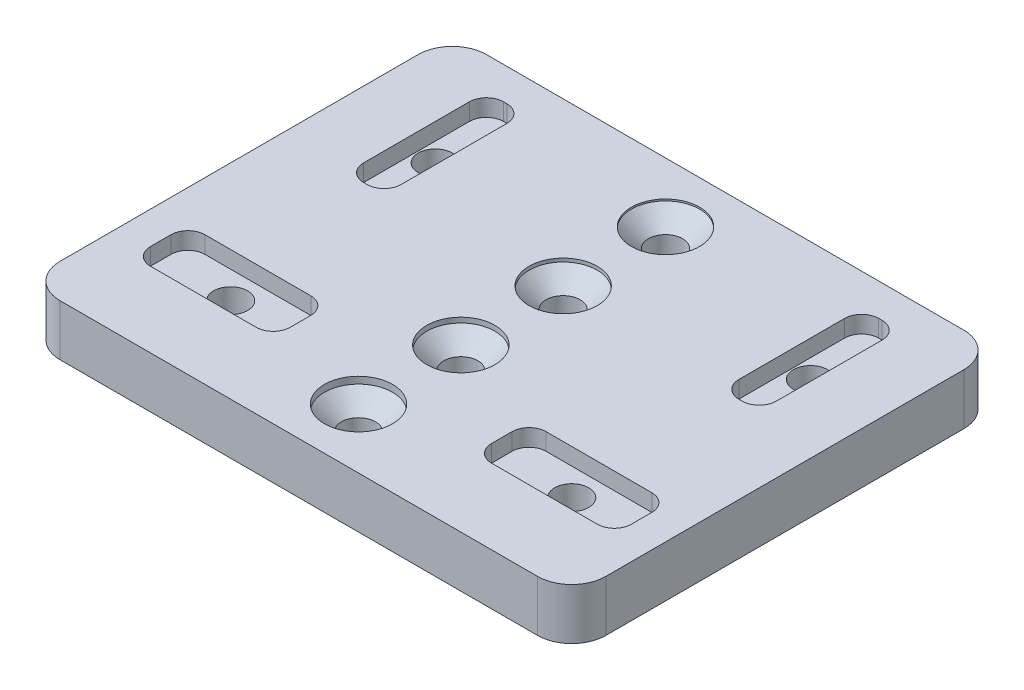
SolidWorks part; units mm, degrees
ref_plane "Front Plane" through (0, 0, 0) normal (0, 0, 1) x (1, 0, 0)
ref_plane "Top Plane" through (0, 0, 0) normal (0, 1, 0) x (1, 0, 0)
ref_plane "Right Plane" through (0, 0, 0) normal (1, 0, 0) x (0, 0, -1)
sketch "Sketch1" plane through (0, 0, 0) normal (0, 1, 0) x (1, 0, 0)
  line L1 (16, 12.5) -> (-16, 12.5)
  line L2 (16, 12.5) -> (16, -12.5)
  line L3 (16, -12.5) -> (-16, -12.5)
  line L4 (-16, 12.5) -> (-16, -12.5)
  line L5 (16, 12.5) -> (-16, -12.5) construction
  line L6 (16, -12.5) -> (-16, 12.5) construction
  point P0 (0, 0)
  dimension "D1" = 32
  dimension "D2" = 25
extrude "Boss-Extrude1" add sketch "Sketch1" along normal blind 3
sketch "Sketch2" plane through (0, 3, 0) normal (0, 1, 0) x (1, 0, 0)
  line L0 (-16, -6.5) -> (16, -6.5) construction
  line L1 (-16, 12.5) -> (-16, -12.5) construction
  line L2 (16, -12.5) -> (16, 12.5) construction
  line L3 (0, 12.5) -> (0, -12.5) construction
  line L4 (16, 12.5) -> (-16, 12.5) construction
  line L5 (-16, -12.5) -> (16, -12.5) construction
  line L6 (14.1, -5.9) -> (14.1, -7.1)
  line L7 (-13.1, -4.9) -> (-6.9, -4.9)
  line L8 (-14.1, -5.9) -> (-14.1, -7.1)
  line L9 (-13.1, -8.1) -> (-6.9, -8.1)
  line L10 (-5.9, -5.9) -> (-5.9, -7.1)
  line L11 (-14.1, -4.9) -> (-5.9, -8.1) construction
  line L12 (-14.1, -8.1) -> (-5.9, -4.9) construction
  line L13 (13.1, -4.9) -> (6.9, -4.9)
  line L14 (5.9, -5.9) -> (5.9, -7.1)
  line L15 (13.1, -8.1) -> (6.9, -8.1)
  line L16 (11.1, 10.6) -> (10.9, 10.6)
  line L17 (-11.1, 10.6) -> (-10.9, 10.6)
  line L18 (-12.1, 9.6) -> (-12.1, 3.4)
  line L19 (-11.1, 2.4) -> (-10.9, 2.4)
  line L20 (-9.9, 9.6) -> (-9.9, 3.4)
  line L21 (-12.1, 10.6) -> (-9.9, 2.4) construction
  line L22 (-12.1, 2.4) -> (-9.9, 10.6) construction
  line L23 (12.1, 9.6) -> (12.1, 3.4)
  line L24 (11.1, 2.4) -> (10.9, 2.4)
  line L25 (9.9, 9.6) -> (9.9, 3.4)
  arc A0 (-14.1, -7.1) -> (-13.1, -8.1) centre (-13.1, -7.1) ccw
  arc A1 (-6.9, -8.1) -> (-5.9, -7.1) centre (-6.9, -7.1) ccw
  arc A2 (-6.9, -4.9) -> (-5.9, -5.9) centre (-6.9, -5.9) cw
  arc A3 (-13.1, -4.9) -> (-14.1, -5.9) centre (-13.1, -5.9) ccw
  arc A4 (14.1, -7.1) -> (13.1, -8.1) centre (13.1, -7.1) cw
  arc A5 (13.1, -4.9) -> (14.1, -5.9) centre (13.1, -5.9) cw
  arc A6 (6.9, -4.9) -> (5.9, -5.9) centre (6.9, -5.9) ccw
  arc A7 (6.9, -8.1) -> (5.9, -7.1) centre (6.9, -7.1) cw
  arc A8 (-10.9, 2.4) -> (-9.9, 3.4) centre (-10.9, 3.4) ccw
  arc A9 (-12.1, 3.4) -> (-11.1, 2.4) centre (-11.1, 3.4) ccw
  arc A10 (-10.9, 10.6) -> (-9.9, 9.6) centre (-10.9, 9.6) cw
  arc A11 (-11.1, 10.6) -> (-12.1, 9.6) centre (-11.1, 9.6) ccw
  arc A12 (11.1, 10.6) -> (12.1, 9.6) centre (11.1, 9.6) cw
  arc A13 (12.1, 3.4) -> (11.1, 2.4) centre (11.1, 3.4) cw
  arc A14 (10.9, 2.4) -> (9.9, 3.4) centre (10.9, 3.4) cw
  arc A15 (10.9, 10.6) -> (9.9, 9.6) centre (10.9, 9.6) ccw
  point P12 (-10, -6.5)
  point P41 (-11, 6.5)
  dimension "D5" = 1
  dimension "D10" = 1
  dimension "D1" = 6
  dimension "D2" = 20
  dimension "D3" = 8.2
  dimension "D4" = 3.2
  dimension "D6" = 8.2
  dimension "D7" = 2.2
  dimension "D8" = 22
  dimension "D9" = 6
extrude "Cut-Extrude1" cut sketch "Sketch2" against normal blind 1
sketch "Sketch3" plane through (0, 2, 0) normal (0, 1, 0) x (1, 0, 0)
  line L0 (-10, -4.9) -> (-10, -8.1) construction
  line L1 (-6.9, -4.9) -> (-13.1, -4.9) construction
  line L2 (-13.1, -8.1) -> (-6.9, -8.1) construction
  line L3 (0, 12.5) -> (0, -12.5) construction
  line L4 (16, 12.5) -> (-16, 12.5) construction
  line L5 (-16, -12.5) -> (16, -12.5) construction
  line L6 (-12.1, 6.5) -> (-9.9, 6.5) construction
  line L7 (-12.1, 9.6) -> (-12.1, 3.4) construction
  line L8 (-9.9, 3.4) -> (-9.9, 9.6) construction
  circle A0 centre (-10, -6.5) radius 1
  circle A1 centre (10, -6.5) radius 1
  circle A2 centre (-11, 6.5) radius 1
  circle A3 centre (11, 6.5) radius 1
  dimension "D1" = 2
extrude "Cut-Extrude2" cut sketch "Sketch3" against normal up to next
sketch "Sketch4" plane through (0, 3, 0) normal (0, 1, 0) x (1, 0, 0)
  line L0 (0, 12.5) -> (0, -12.5) construction
  line L1 (16, 12.5) -> (-16, 12.5) construction
  line L2 (-16, -12.5) -> (16, -12.5) construction
  line L3 (-16, 0) -> (16, 0) construction
  line L6 (-16, 12.5) -> (-16, -12.5) construction
  line L7 (16, -12.5) -> (16, 12.5) construction
  circle A0 centre (0, -9) radius 1
  circle A2 centre (0, -3) radius 1
  circle A3 centre (0, 3) radius 1
  circle A4 centre (0, 9) radius 1
  dimension "D1" = 2
  dimension "D3" = 6
  dimension "D2" = 4
extrude "Cut-Extrude3" cut sketch "Sketch4" against normal up to next
hole_wizard "CSK for M2 Flat Head Machine Screw1" positions "Sketch5" profile "Sketch6" countersink size "M2" standard "ANSI Metric" end condition up to next
sketch "Sketch5" plane through (0, 3, 0) normal (0, 1, 0) x (1, 0, 0)
  point P0 (0, 9)
sketch "Sketch6" plane through (0, 3, -9) normal (1, 0, 0) x (0, 0, 1)
  line L0 (0, 0) -> (0, 3)
  line L1 (0, 3) -> (1, 3)
  line L2 (1, 3) -> (1, 1.1)
  line L3 (1, 1.1) -> (2, 0.1)
  line L4 (2, 0.1) -> (2, 0)
  line L6 (2, 0) -> (0, 0)
  line L7 (-1, 1.1) -> (-2, 0.1) construction
  line L11 (0, -6.35) -> (0, 107.95) construction
  dimension "Thru Hole Dia." = 2
  dimension "Thru Hole Depth" = 3
  dimension "C'Sink Dia." = 4
  dimension "C'Sink Angle" = 90
  dimension "Head Clearance" = 0.1
hole_wizard "CSK for M2 Flat Head Machine Screw2" positions "Sketch7" profile "Sketch8" countersink size "M2" standard "ANSI Metric" end condition up to next
sketch "Sketch7" plane through (0, 3, 0) normal (0, 1, 0) x (1, 0, 0)
  point P0 (0, 3)
sketch "Sketch8" plane through (0, 3, -3) normal (1, 0, 0) x (0, 0, 1)
  line L0 (0, 0) -> (0, 3)
  line L1 (0, 3) -> (1, 3)
  line L2 (1, 3) -> (1, 1.2)
  line L3 (1, 1.2) -> (2, 0.2)
  line L4 (2, 0.2) -> (2, 0)
  line L6 (2, 0) -> (0, 0)
  line L7 (-1, 1.2) -> (-2, 0.2) construction
  line L11 (0, -6.35) -> (0, 107.95) construction
  dimension "Thru Hole Dia." = 2
  dimension "Thru Hole Depth" = 3
  dimension "C'Sink Dia." = 4
  dimension "C'Sink Angle" = 90
  dimension "Head Clearance" = 0.2
hole_wizard "CSK for M2 Flat Head Machine Screw3" positions "Sketch9" profile "Sketch10" countersink size "M2" standard "ANSI Metric" end condition up to next
sketch "Sketch9" plane through (0, 3, 0) normal (0, 1, 0) x (1, 0, 0)
  point P0 (0, -3)
sketch "Sketch10" plane through (0, 3, 3) normal (1, 0, 0) x (0, 0, 1)
  line L0 (0, 0) -> (0, 3)
  line L1 (0, 3) -> (1, 3)
  line L2 (1, 3) -> (1, 1.3)
  line L3 (1, 1.3) -> (2, 0.3)
  line L4 (2, 0.3) -> (2, 0)
  line L6 (2, 0) -> (0, 0)
  line L7 (-1, 1.3) -> (-2, 0.3) construction
  line L11 (0, -6.35) -> (0, 107.95) construction
  dimension "Thru Hole Dia." = 2
  dimension "Thru Hole Depth" = 3
  dimension "C'Sink Dia." = 4
  dimension "C'Sink Angle" = 90
  dimension "Head Clearance" = 0.3
hole_wizard "CSK for M2 Flat Head Machine Screw4" positions "Sketch11" profile "Sketch12" countersink size "M2" standard "ANSI Metric" end condition up to next
sketch "Sketch11" plane through (0, 3, 0) normal (0, 1, 0) x (1, 0, 0)
  point P0 (0, -9)
sketch "Sketch12" plane through (0, 3, 9) normal (1, 0, 0) x (0, 0, 1)
  line L0 (0, 0) -> (0, 3)
  line L1 (0, 3) -> (1, 3)
  line L2 (1, 3) -> (1, 1.4)
  line L3 (1, 1.4) -> (2, 0.4)
  line L4 (2, 0.4) -> (2, 0)
  line L6 (2, 0) -> (0, 0)
  line L7 (-1, 1.4) -> (-2, 0.4) construction
  line L11 (0, -6.35) -> (0, 107.95) construction
  dimension "Thru Hole Dia." = 2
  dimension "Thru Hole Depth" = 3
  dimension "C'Sink Dia." = 4
  dimension "C'Sink Angle" = 90
  dimension "Head Clearance" = 0.4
fillet "Fillet1" radius 2 4 edges at (-16, 1.5, -12.5) (16, 1.5, -12.5) (16, 1.5, 12.5) (-16, 1.5, 12.5)
